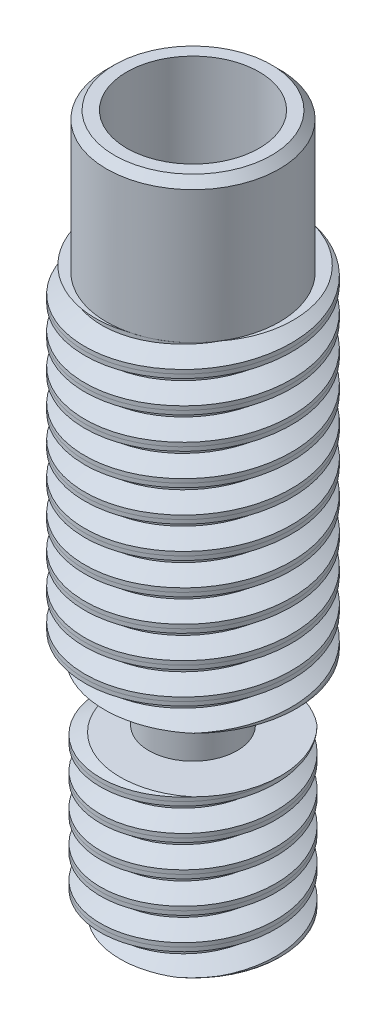
SolidWorks part; units mm, degrees
material "AISI 304"
ref_plane "Plano frontal" through (0, 0, 0) normal (0, 0, 1) x (1, 0, 0)
ref_plane "Plano superior" through (0, 0, 0) normal (0, 1, 0) x (1, 0, 0)
ref_plane "Plano direito" through (0, 0, 0) normal (1, 0, 0) x (0, 0, -1)
sketch "Esboço1" plane through (0, 0, 0) normal (0, 0, 1) x (1, 0, 0)
  line L0 (12.7419, 22.335) -> (51.682, 22.335) construction
  line L1 (11.878, 36.795) -> (11.878, 13.8126) construction
  line L2 (9.778, 36.3023) -> (9.388, 36.3023)
  line L3 (9.138, 36.0523) -> (9.138, 31.8501)
  line L4 (9.138, 31.8501) -> (8.378, 31.8501)
  line L5 (8.378, 31.8501) -> (8.378, 21.5023)
  line L6 (8.378, 21.5023) -> (10.478, 21.5023)
  line L7 (10.478, 21.5023) -> (10.478, 19.4023)
  line L8 (10.478, 19.4023) -> (8.878, 19.4023)
  line L9 (8.878, 19.4023) -> (8.878, 14.6523)
  line L10 (9.128, 14.4023) -> (10.878, 14.4023)
  line L11 (9.778, 36.3023) -> (9.778, 31.8501)
  line L12 (9.778, 31.8501) -> (10.878, 31.0799)
  line L13 (10.878, 31.0799) -> (10.878, 14.4023)
  line L14 (9.138, 31.8501) -> (9.778, 31.8501) construction
  line L15 (8.878, 14.6523) -> (9.128, 14.4023)
  line L16 (9.388, 36.3023) -> (9.138, 36.0523)
  point P5 (9.138, 36.3023)
  point P13 (8.878, 14.4023)
  dimension "D1" = 14.8
  dimension "D2" = 2.1
  dimension "D3" = 2.1
  dimension "D4" = 7.1
  dimension "D5" = 1.4
  dimension "D6" = 3.5
  dimension "D7" = 3
  dimension "D8" = 1
  dimension "D9" = 0.25
  dimension "D10" = 45
  dimension "D11" = 0.25
  dimension "D12" = 45
  dimension "D13" = 2.74
revolve "Revolução1" add sketch "Esboço1" angle 360 about L1
cosmetic thread "Representação de rosca1" [suppressed] parameters "D2"=4.891
cosmetic thread "Representação de rosca2" [suppressed] parameters "D2"=4.891
sketch "Esboço2" plane through (0, 0, 0) normal (0, 0, 1) x (1, 0, 0)
  line L0 (14.618, 36.0523) -> (9.138, 36.0523) construction
  line L1 (11.378, 36.5523) -> (12.378, 36.5523)
  line L2 (11.378, 36.5523) -> (11.378, 35.5523)
  line L3 (11.378, 35.5523) -> (12.378, 35.5523)
  line L4 (12.378, 36.5523) -> (12.378, 35.5523)
  line L5 (11.378, 36.5523) -> (12.378, 35.5523) construction
  line L6 (11.378, 35.5523) -> (12.378, 36.5523) construction
  point P0 (11.878, 36.0523)
  dimension "D1" = 1
  dimension "D2" = 1
extrude "Corte-extrusão1" [suppressed] cut sketch "Esboço2" against normal blind 10 from offset 12.5
chamfer "Chanfro1" distance 0.05 angle 45 3 edges at (11.878, 31.8501, 3.5) (11.878, 19.4023, 3) (11.878, 21.5023, 3.5)
sketch "Esboço3" plane through (0, 0, 0) normal (0, 0, 1) x (1, 0, 0)
  line L0 (8.878, 19.3523) -> (8.878, 14.6523) construction
  line L2 (9.6357, 14.3398) -> (9.0945, 14.0273)
  line L3 (8.878, 13.9023) -> (8.878, 14.9023)
  line L4 (9.6357, 14.4023) -> (8.878, 14.4023) construction
  line L5 (9.6357, 14.4648) -> (9.0945, 14.7773)
  line L6 (9.6357, 14.4648) -> (9.6357, 14.3398)
  line L7 (8.878, 13.9023) -> (9.0945, 13.9023)
  line L8 (9.0945, 13.9023) -> (9.0945, 14.0273)
  line L9 (9.0945, 14.9023) -> (9.0945, 14.7773)
  line L10 (8.878, 14.9023) -> (9.0945, 14.9023)
  dimension "D2" = 0.5
  dimension "D3" = 0.125
  dimension "D4" = 0.125
sketch "Esboço4" plane through (0, 14.4023, 0) normal (0, -1, 0) x (1, 0, 0)
  circle A0 centre (11.878, 0) radius 3 construction
  circle A1 centre (11.878, 0) radius 3
curve "Hélice/Espiral2" pitch 1 height 6.5 radius 3 centre (11.878, 14.4023, 0) axis (0, 1, 0) start towards (0, 0, -1)
sweep "Varredura de corte4" cut profiles "Esboço3" path "Hélice/Espiral2" align with end faces yes
sketch "Esboço5" plane through (0, 0, 0) normal (0, 0, 1) x (1, 0, 0)
  line L0 (8.378, 21.7503) -> (8.378, 21.1852) construction
  line L1 (8.378, 31.8001) -> (8.378, 21.5523) construction
  line L2 (9.244, 21.8694) -> (9.244, 21.1852) construction
  line L3 (9.1357, 21.4398) -> (8.5945, 21.1273)
  line L4 (8.428, 21.5023) -> (15.328, 21.5023) construction
  line L5 (8.378, 21.0023) -> (8.378, 22.0023)
  line L6 (8.378, 21.5023) -> (9.244, 21.5023) construction
  line L7 (9.1357, 21.5648) -> (9.1357, 21.4398)
  line L8 (8.378, 21.0023) -> (8.5945, 21.0023)
  line L9 (8.5945, 21.0023) -> (8.5945, 21.1273)
  line L10 (8.378, 21.2542) -> (8.378, 21.8194) construction
  line L11 (8.5945, 22.0023) -> (8.5945, 21.8773)
  line L12 (8.378, 22.0023) -> (8.5945, 22.0023)
  line L13 (9.1357, 21.5648) -> (8.5945, 21.8773)
  point P21 (9.1357, 21.5023)
  dimension "D1" = 0.866
  dimension "D2" = 0.5
  dimension "D3" = 0.0625
  dimension "D4" = 0.125
sketch "Esboço6" plane through (0, 21.5023, 0) normal (0, -1, 0) x (1, 0, 0)
  circle A0 centre (11.878, 0) radius 3.5 construction
  circle A1 centre (11.878, 0) radius 3.5
curve "Hélice/Espiral3" pitch 1 height 12.25 radius 3.5 centre (11.878, 21.5023, 0) axis (0, 1, 0) start towards (0, 0, -1)
sweep "Varredura de corte5" cut profiles "Esboço5" path "Hélice/Espiral3" align with end faces yes
chamfer "Chanfro2" distance 0.1 angle 45 1 edges at (11.878, 14.4023, 1)
